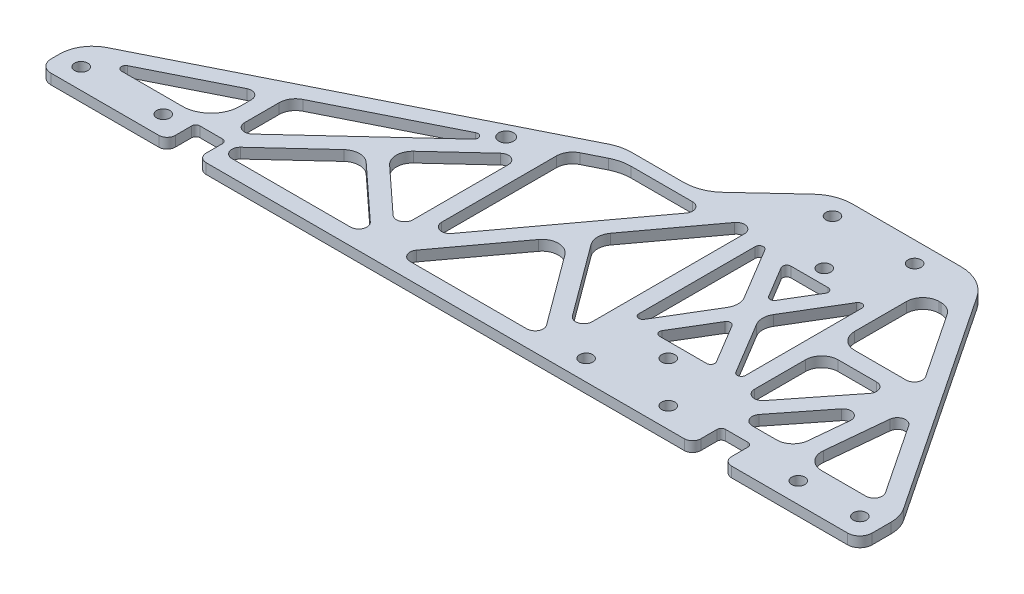
SolidWorks part; units mm, degrees
ref_plane "Front Plane" through (0, 0, 0) normal (0, 0, 1) x (1, 0, 0)
ref_plane "Top Plane" through (0, 0, 0) normal (0, 1, 0) x (1, 0, 0)
ref_plane "Right Plane" through (0, 0, 0) normal (1, 0, 0) x (0, 0, -1)
sketch "Sketch1" plane through (0, 0, 0) normal (0, 1, 0) x (1, 0, 0)
  line L0 (0, 0) -> (254, 0)
  line L2 (203.2, 88.9) -> (152.4, 88.9)
  line L4 (0, 0) -> (0, 12.7)
  line L5 (0, 12.7) -> (152.4, 88.9)
  line L6 (203.2, 88.9) -> (254, 12.7)
  line L7 (254, 12.7) -> (254, 0)
  line L8 (0, 6.35) -> (44.45, 6.35) construction
  line L9 (254, 6.35) -> (228.6, 6.35) construction
  line L10 (139.7, 82.55) -> (207.4333, 82.55) construction
  line L11 (44.45, 0) -> (44.45, 34.925) construction
  line L12 (156.6333, 12.7) -> (154.0933, 7.62)
  line L13 (224.7006, 47.4909) -> (221.314, 12.7) construction
  line L20 (127, 76.2) -> (211.6667, 76.2)
  line L21 (154.0933, 76.2) -> (101.6, 5.08) construction
  line L22 (154.0933, 12.7) -> (154.0933, 7.62)
  line L23 (247.8946, 12.7) -> (194.7333, 12.7)
  line L24 (224.7006, 47.4909) -> (197.2733, 12.7) construction
  line L28 (224.7006, 47.4909) -> (194.7333, 47.4909) construction
  line L31 (5.08, 9.5604) -> (153.5992, 83.82)
  line L32 (200.4813, 83.82) -> (153.5992, 83.82)
  line L33 (200.4813, 83.82) -> (248.92, 11.1619)
  line L34 (248.92, 11.1619) -> (248.92, 5.08)
  line L35 (5.08, 5.08) -> (248.92, 5.08)
  line L36 (5.08, 5.08) -> (5.08, 9.5604)
  line L37 (101.6, 5.08) -> (101.6, 57.8204) construction
  line L39 (127.8467, 40.64) -> (154.0933, 5.08) construction
  line L40 (101.6, 57.8204) -> (44.45, 5.08) construction
  line L41 (73.025, 31.4502) -> (101.6, 5.08) construction
  line L42 (154.0933, 7.62) -> (154.0933, 5.08)
  line L83 (152.8233, 5.08) -> (150.2833, 0)
  line L84 (125.803, 39.1316) -> (152.0497, 3.5716)
  line L107 (152.0497, 77.7084) -> (99.5564, 6.5884)
  line L108 (156.6333, 76.2) -> (194.7333, 12.7) construction
  line L113 (194.7333, 76.2) -> (156.6333, 12.7) construction
  line L117 (104.14, 5.08) -> (104.14, 63.6207)
  line L118 (156.6333, 12.7) -> (194.7333, 12.7)
  line L119 (194.7333, 12.7) -> (201.0833, 0)
  line L120 (154.0933, 6.35) -> (197.9083, 6.35) construction
  line L126 (192.5553, 77.5068) -> (154.4553, 14.0068)
  line L127 (154.4553, 74.8932) -> (192.5553, 11.3932)
  line L128 (156.6333, 12.7) -> (156.6333, 76.2) construction
  line L129 (194.7333, 12.7) -> (194.7333, 76.2) construction
  line L130 (197.2733, 12.7) -> (197.2733, 76.2)
  line L131 (159.1733, 12.7) -> (159.1733, 76.2)
  line L132 (192.1933, 12.7) -> (192.1933, 76.2)
  line L133 (154.0933, 12.7) -> (154.0933, 76.2)
  line L147 (196.9114, 74.8932) -> (158.8114, 11.3932)
  line L148 (158.8114, 77.5068) -> (196.9114, 14.0068)
  line L154 (104.14, 63.6207) -> (42.7274, 6.9466)
  line L155 (71.3024, 29.5836) -> (99.8774, 3.2134)
  line L156 (224.7006, 50.0309) -> (194.7333, 50.0309)
  line L157 (222.7059, 49.0635) -> (195.2786, 14.2725)
  line L158 (197.2733, 12.7) -> (197.2733, 7.62)
  line L159 (222.1726, 47.737) -> (218.7859, 12.9461)
  line L160 (129.8903, 42.1484) -> (156.137, 6.5884)
  line L163 (156.137, 74.6916) -> (103.6436, 3.5716)
  line L164 (99.06, 5.08) -> (99.06, 52.0201)
  line L165 (99.06, 52.0201) -> (46.1726, 3.2134)
  line L166 (175.6833, 19.05) -> (162.9833, 6.35) construction
  line L167 (175.6833, 19.05) -> (188.3833, 6.35) construction
  line L168 (162.9833, 82.55) -> (175.6833, 67.31) construction
  line L169 (175.6833, 67.31) -> (188.3833, 82.55) construction
  line L170 (161.6625, 21.082) -> (189.7041, 21.082) construction
  line L171 (161.6625, 23.622) -> (189.7041, 23.622)
  line L172 (163.1865, 65.278) -> (188.1801, 65.278) construction
  line L173 (163.1865, 62.738) -> (188.1801, 62.738)
  line L174 (74.7476, 33.3168) -> (103.3226, 6.9466)
  line L175 (224.7006, 44.9509) -> (194.7333, 44.9509)
  line L176 (226.6953, 45.9184) -> (199.268, 11.1275)
  line L177 (227.2287, 47.2449) -> (223.842, 12.4539)
  line L178 (8.8192, 11.43) -> (44.45, 11.43)
  line L179 (46.99, 0) -> (46.99, 34.925)
  line L180 (41.91, 0) -> (41.91, 34.925)
  line L181 (198.2745, 13.97) -> (221.4376, 13.97)
  line L182 (115.4992, 64.77) -> (145.6569, 64.77)
  circle A0 centre (6.7733, 6.35) radius 2.032
  circle A1 centre (32.1733, 6.35) radius 2.032
  circle A2 centre (228.6, 6.35) radius 2.032
  circle A3 centre (247.65, 6.35) radius 2.032
  circle A4 centre (162.9833, 82.55) radius 2.032
  circle A5 centre (188.3833, 82.55) radius 2.032
  circle A28 centre (162.9833, 6.35) radius 2.032
  circle A29 centre (188.3833, 6.35) radius 2.032
  arc A32 (197.2733, 12.7) -> (192.1933, 12.7) centre (194.7333, 12.7) cw
  arc A33 (197.2733, 76.2) -> (192.1933, 76.2) centre (194.7333, 76.2) ccw
  arc A34 (159.1733, 12.7) -> (154.0933, 12.7) centre (156.6333, 12.7) cw
  arc A35 (159.1733, 76.2) -> (154.0933, 76.2) centre (156.6333, 76.2) ccw
  arc A45 (192.5553, 77.5068) -> (196.9114, 74.8932) centre (194.7333, 76.2) cw
  arc A46 (154.4553, 14.0068) -> (158.8114, 11.3932) centre (156.6333, 12.7) ccw
  arc A47 (154.4553, 74.8932) -> (158.8114, 77.5068) centre (156.6333, 76.2) cw
  arc A48 (192.5553, 11.3932) -> (196.9114, 14.0068) centre (194.7333, 12.7) ccw
  circle A59 centre (175.6833, 19.05) radius 2.032
  circle A60 centre (175.6833, 67.31) radius 2.032
  arc A61 (125.803, 39.1316) -> (129.8903, 42.1484) centre (127.8467, 40.64) cw
  arc A62 (152.0497, 3.5716) -> (156.137, 6.5884) centre (154.0933, 5.08) ccw
  arc A63 (152.0497, 77.7084) -> (156.137, 74.6916) centre (154.0933, 76.2) cw
  arc A64 (99.5564, 6.5884) -> (103.6436, 3.5716) centre (101.6, 5.08) ccw
  arc A65 (104.14, 5.08) -> (99.06, 5.08) centre (101.6, 5.08) cw
  arc A66 (42.7274, 6.9466) -> (46.1726, 3.2134) centre (44.45, 5.08) ccw
  arc A67 (71.3024, 29.5836) -> (74.7476, 33.3168) centre (73.025, 31.4502) cw
  arc A68 (99.8774, 3.2134) -> (103.3226, 6.9466) centre (101.6, 5.08) ccw
  arc A69 (224.7006, 50.0309) -> (224.7006, 44.9509) centre (224.7006, 47.4909) cw
  arc A70 (194.7333, 50.0309) -> (194.7333, 44.9509) centre (194.7333, 47.4909) ccw
  arc A71 (222.7059, 49.0635) -> (226.6953, 45.9184) centre (224.7006, 47.4909) cw
  arc A72 (195.2786, 14.2725) -> (199.268, 11.1275) centre (197.2733, 12.7) ccw
  arc A73 (222.1726, 47.737) -> (227.2287, 47.2449) centre (224.7006, 47.4909) cw
  arc A74 (218.7859, 12.9461) -> (223.842, 12.4539) centre (221.314, 12.7) ccw
  arc A75 (46.99, 0) -> (41.91, 0) centre (44.45, 0) cw
  arc A76 (46.99, 34.925) -> (41.91, 34.925) centre (44.45, 34.925) ccw
  dimension "D7" = 4.064
  dimension "D8" = 25.4
  dimension "D9" = 130.81
  dimension "D10" = 19.05
  dimension "D11" = 6.35
  dimension "D13" = 19.05
  dimension "D1" = 254
  dimension "D2" = 50.8
  dimension "D3" = 88.9
  dimension "D4" = 152.4
  dimension "D5" = 12.7
  dimension "D6" = 6.35
  dimension "D12" = 25.4
  dimension "D14" = 44.45
  dimension "D15" = 12.7
  dimension "D16" = 57.15
  dimension "D18" = 12.7
  dimension "D19" = 2.54
  dimension "D20" = 50.8
  dimension "D21" = 25.4
  dimension "D22" = 2.54
  dimension "D23" = 6.35
  dimension "D24" = 2.54
  dimension "D29" = 6.35
  dimension "D30" = 38.1
  dimension "D31" = 25.4
  dimension "D32" = 6.35
  dimension "D33" = 2.54
  dimension "D36" = 12.7
  dimension "D38" = 15.24
  dimension "D39" = 2.54
  dimension "D40" = 2.54
  dimension "D27" = 1.27
  dimension "D28" = 19.05
  dimension "D17" = 5.08
  dimension "D25" = 2.54
  dimension "D26" = 2.54
  dimension "D37" = 2.54
extrude "Boss-Extrude1" add sketch "Sketch1" along normal blind 3.175 contours L0 L7 L6 L2 L5 L4 | A0 | A1 | A5 | A4 | A2 | A3
extrude "Cut-Extrude2" cut sketch "Sketch1<3>" along normal through all contours L154 L31 L11 | L155 L165 L35 | L165 L174 L164 | L117 L107 L20 L31 | L84 L163 L35 | L133 L163 L160 L22 | L157 L175 L130 | L156 L33 L20 L130 | L147 L148 L132 | L131 L126 L127 | L173 L148 L126 | L147 L171 L127 | L33 L177 L23 | L178 L180 L31 | L176 L181 L159 | A28 | A59 | A29 | A60 region at (30.8797, 0, -16.9451) region at (73.025, 0, -12.718) region at (62.4687, 0, -31.7097) region at (127.8467, 0, -15.5076) region at (91.6301, 0, -31.4502) region at (117.2277, 0, -46.9301) region at (206.5243, 0, -60.8789) region at (146.3968, 0, -40.64) region at (204.6702, 0, -35.5682) region at (175.6833, 0, -28.919) region at (187.6774, 0, -44.45) region at (213.9093, 0, -22.3524) region at (163.6893, 0, -44.45) region at (232.896, 0, -23.1836) region at (175.6833, 0, -58.2876)
sketch "Sketch1<3>" plane through (0, 0, 0) normal (0, 1, 0) x (1, 0, 0) same geometry as "Sketch1"
fillet "Fillet1" radius 3.81 2 edges at (254, 1.5875, 0) (0, 1.5875, 0)
fillet "Fillet2" radius 10.16 2 edges at (254, 1.5875, -12.7) (0, 1.5875, -12.7)
fillet "Fillet3" radius 12.7 2 edges at (203.2, 1.5875, -88.9) (152.4, 1.5875, -88.9)
fillet "Fillet4" radius 1.27 12 edges at (159.1733, 1.5875, -67.0298) (192.1933, 1.5875, -67.0298) (192.1933, 1.5875, -21.8702) (159.1733, 1.5875, -21.8702) (183.694, 1.5875, -62.738) (167.6727, 1.5875, -62.738) (175.6833, 1.5875, -49.3869) (185.218, 1.5875, -23.622) (166.1487, 1.5875, -23.622) (175.6833, 1.5875, -39.5131) (93.426, 1.5875, -53.7334) (8.8192, 1.5875, -11.43)
fillet "Fillet5" radius 2.54 19 edges at (223.0073, 1.5875, -50.0309) (247.8946, 1.5875, -12.7) (226.9275, 1.5875, -44.1507) (221.3335, 1.5875, -39.1171) (197.2733, 1.5875, -16.8027) (219.4639, 1.5875, -44.9509) (104.14, 1.5875, -12.7984) (99.06, 1.5875, -52.0201) (48.1953, 1.5875, -5.08) (97.8547, 1.5875, -5.08) (99.06, 1.5875, -10.8803) (104.7569, 1.5875, -5.08) (150.9364, 1.5875, -5.08) (154.0933, 1.5875, -9.3572) (154.0933, 1.5875, -71.9228) (41.91, 1.5875, -27.9754) (46.99, 1.5875, -10.8803) (201.5089, 1.5875, -13.97) (142.5, 1.5875, -64.77)
fillet "Fillet6" radius 5.08 14 edges at (172.7212, 1.5875, -44.45) (178.6455, 1.5875, -44.45) (223.866, 1.5875, -12.7) (197.2733, 1.5875, -50.0309) (197.2733, 1.5875, -44.9509) (197.2733, 1.5875, -76.2) (205.5613, 1.5875, -76.2) (73.025, 1.5875, -27.9939) (76.7703, 1.5875, -31.4502) (104.14, 1.5875, -59.0904) (131.0036, 1.5875, -40.64) (127.8467, 1.5875, -36.3628) (46.99, 1.5875, -30.5154) (218.8856, 1.5875, -13.97)
fillet "Fillet7" radius 12.7 1 edges at (115.4992, 1.5875, -64.77)
fillet "Fillet10" radius 8.89 1 edges at (41.91, 1.5875, -11.43)
sketch "Sketch4" plane through (0, 3.175, 0) normal (0, 1, 0) x (1, 0, 0)
  line L0 (118.4973, 64.77) -> (137.4682, 64.77) construction
  line L1 (118.4973, 64.77) -> (137.4682, 64.77)
  line L2 (118.4973, 68.58) -> (113.3689, 68.58) construction
  line L4 (137.4682, 64.77) -> (163.3832, 88.9)
  line L5 (118.4973, 68.58) -> (111.76, 68.58)
  line L6 (252.2936, 15.2596) -> (206.9702, 83.2447)
  line L7 (196.4032, 88.9) -> (155.3981, 88.9)
  line L8 (149.7185, 87.5592) -> (5.6163, 15.5082)
  line L9 (0, 6.4208) -> (0, 3.81)
  line L10 (3.81, 0) -> (250.19, 0)
  line L11 (254, 3.81) -> (254, 9.6238)
  line L12 (252.2936, 15.2596) -> (206.9702, 83.2447)
  line L13 (196.4032, 88.9) -> (155.3981, 88.9)
  line L14 (149.7185, 87.5592) -> (5.6163, 15.5082)
  line L15 (0, 6.4208) -> (0, 3.81)
  line L16 (3.81, 0) -> (250.19, 0)
  line L17 (254, 3.81) -> (254, 9.6238)
  line L18 (118.4973, 68.58) -> (135.9691, 68.58)
  line L19 (135.9691, 68.58) -> (157.7922, 88.9)
  line L20 (137.4682, 64.77) -> (155.4291, 81.4938) construction
  line L21 (196.4032, 88.9) -> (155.3981, 88.9) construction
  line L22 (135.9691, 68.58) -> (152.8328, 84.2822) construction
  line L23 (5.6163, 15.5082) -> (149.7185, 87.5592) construction
  line L29 (118.4973, 64.77) -> (113.3689, 64.77) construction
  arc A6 (206.9702, 83.2447) -> (196.4032, 88.9) centre (196.4032, 76.2) ccw
  arc A7 (155.3981, 88.9) -> (149.7185, 87.5592) centre (155.3981, 76.2) ccw
  arc A8 (5.6163, 15.5082) -> (0, 6.4208) centre (10.16, 6.4208) ccw
  arc A9 (0, 3.81) -> (3.81, 0) centre (3.81, 3.81) ccw
  arc A10 (250.19, 0) -> (254, 3.81) centre (250.19, 3.81) ccw
  arc A11 (254, 9.6238) -> (252.2936, 15.2596) centre (243.84, 9.6238) ccw
  arc A12 (206.9702, 83.2447) -> (196.4032, 88.9) centre (196.4032, 76.2) ccw
  arc A13 (155.3981, 88.9) -> (149.7185, 87.5592) centre (155.3981, 76.2) ccw
  arc A14 (5.6163, 15.5082) -> (0, 6.4208) centre (10.16, 6.4208) ccw
  arc A15 (0, 3.81) -> (3.81, 0) centre (3.81, 3.81) ccw
  arc A16 (250.19, 0) -> (254, 3.81) centre (250.19, 3.81) ccw
  arc A17 (254, 9.6238) -> (252.2936, 15.2596) centre (243.84, 9.6238) ccw
  dimension "D2" = 3.81
  dimension "D4" = 33.02
  dimension "D1" = 0
extrude "Cut-Extrude5" cut sketch "Sketch4" against normal through all and the other way through all contours L13 A13 L14 L5 L18 L19 region at (136.1343, 3.175, -76.5597)
fillet "Fillet11" radius 12.7 3 edges at (111.76, 1.5875, -68.58) (157.7922, 1.5875, -88.9) (135.9691, 1.5875, -68.58)
sketch "Sketch2" plane through (0, 3.175, 0) normal (0, 1, 0) x (1, 0, 0)
  line L0 (39.6875, 0) -> (39.6875, 8.89)
  line L1 (3.81, 0) -> (250.19, 0) construction
  line L2 (39.6875, 8.89) -> (49.2125, 8.89)
  line L3 (49.2125, 8.89) -> (49.2125, 0)
  line L4 (0, 3.81) -> (0, 6.4208) construction
  line L5 (202.2475, 0) -> (202.2475, 8.89)
  line L6 (202.2475, 8.89) -> (211.7725, 8.89)
  line L7 (211.7725, 8.89) -> (211.7725, 0)
  line L8 (254, 9.6238) -> (254, 3.81) construction
  line L9 (3.81, 0) -> (250.19, 0)
  dimension "D1" = 39.6875
  dimension "D2" = 9.525
  dimension "D3" = 8.89
  dimension "D4" = 42.2275
extrude "Cut-Extrude3" cut sketch "Sketch2" against normal through all contours L0 L9 L3 L2 | L5 L9 L7 L6 region at (207.01, 3.175, -4.445) region at (44.45, 3.175, -4.445)
fillet "Fillet8" radius 1.27 4 edges at (211.7725, 1.5875, -8.89) (202.2475, 1.5875, -8.89) (49.2125, 1.5875, -8.89) (39.6875, 1.5875, -8.89)
fillet "Fillet9" radius 2.54 4 edges at (49.2125, 1.5875, 0) (39.6875, 1.5875, 0) (211.7725, 1.5875, 0) (202.2475, 1.5875, 0)
sketch "Sketch3" plane through (0, 3.175, 0) normal (0, 1, 0) x (1, 0, 0)
  line L0 (322.9659, 17.0563) -> (94.1827, 68.4886) construction
  circle A0 centre (322.9659, 17.0563) radius 2.286 construction
  circle A1 centre (322.9659, 17.0563) radius 2.286
  circle A2 centre (91.2882, 53.2846) radius 2.286
  arc A4 (94.1827, 68.4886) -> (88.6111, 9.0045) centre (322.9659, 17.0563) ccw construction
  dimension "D1" = 234.4931
  dimension "D2" = 4.572
extrude "Cut-Extrude4" cut sketch "Sketch3" against normal up to surface (3.175 mm away) contours A2 region at (91.2882, 3.175, -53.2846) up to face at (233.1564, 0, -22.5815)
